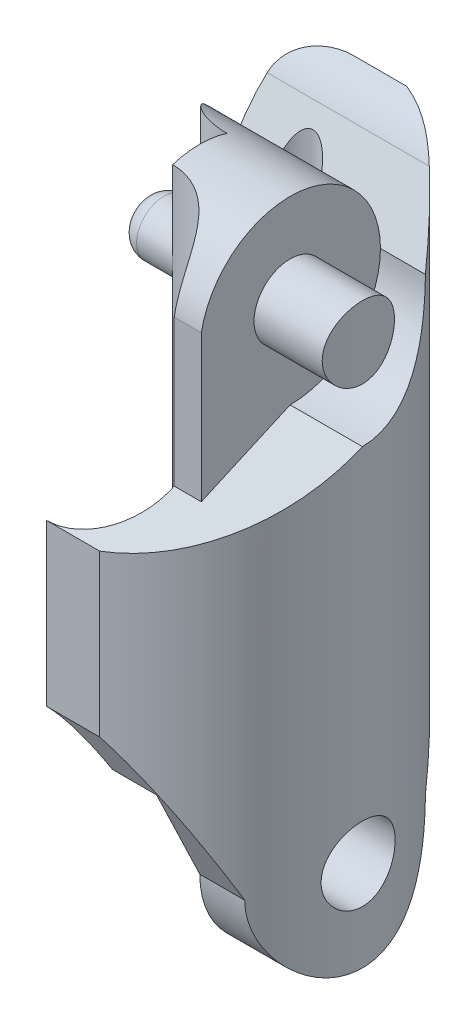
SolidWorks part; units mm, degrees
ref_plane "Front Plane" through (0, 0, 0) normal (0, 0, 1) x (1, 0, 0)
ref_plane "Top Plane" through (0, 0, 0) normal (0, 1, 0) x (1, 0, 0)
ref_plane "Right Plane" through (0, 0, 0) normal (1, 0, 0) x (0, 0, -1)
sketch "Sketch1" plane through (0, 0, 0) normal (0, 1, 0) x (1, 0, 0)
  line L0 (-2.958, 8.5) -> (2.958, 8.5)
  line L1 (-2.958, -8.5) -> (2.958, -8.5)
  arc A0 (-2.958, 8.5) -> (-2.958, -8.5) centre (0, 0) ccw
  arc A1 (2.958, 8.5) -> (2.958, -8.5) centre (0, 0) cw
  point P9 (-9, 0)
  point P10 (9, 0)
  dimension "D1" = 18
  dimension "D2" = 17
extrude "Boss-Extrude1" add sketch "Sketch1" along normal blind 35
sketch "Sketch2" plane through (0, 0, 0) normal (0, -1, 0) x (1, 0, 0)
  circle A0 centre (0, -5) radius 1.27
  circle A1 centre (0, 5) radius 1.27
  dimension "D1" = 2.54
  dimension "D2" = 5
  dimension "D3" = 5
extrude "Cut-Extrude1" cut sketch "Sketch2" against normal blind 35
sketch "Sketch3" plane through (0, 0, -8.5) normal (0, 0, -1) x (-1, 0, 0)
  line L0 (5, 0) -> (5, 10)
  line L1 (5, 10) -> (-5, 10)
  line L2 (-5, 10) -> (-5, 0)
  line L3 (5, 0) -> (-5, 0)
  line L4 (-2.958, 0) -> (2.958, 0) construction
  point P10 (0, 0)
  dimension "D1" = 10
  dimension "D2" = 10
extrude "Cut-Extrude2" cut sketch "Sketch3" against normal up to surface (17 mm away) up to face at (0, 17.5, 8.5)
sketch "Sketch4" plane through (5, 0, 0) normal (-1, 0, 0) x (0, 0, 1)
  line L0 (-7.4833, 10) -> (-5, 5)
  line L1 (8.5, 12.3086) -> (5, 5)
  line L2 (7.4833, 0) -> (-7.4833, 0) construction
  line L3 (-7.4833, 10) -> (-9.8579, -1.8222)
  line L4 (-9.8579, -1.8222) -> (9.8579, -1.8222)
  line L6 (8.5, 35) -> (8.5, 10) construction
  line L7 (9.8579, -1.8222) -> (8.5, 12.3086)
  arc A0 (-5, 5) -> (5, 5) centre (0, 5) ccw
  circle A1 centre (0, 5) radius 2.05
  point P7 (0, 0)
  dimension "D1" = 4.1
  dimension "D2" = 5
  dimension "D3" = 12.0584
  dimension "D4" = 37.769
extrude "Cut-Extrude3" cut sketch "Sketch4" against normal mid plane 35
ref_plane "Plane1" through (-2.958, 0, 0) normal (-1, 0, 0) x (0, 0, 1)
sketch "Sketch6" plane through (-2.958, 0, 0) normal (-1, 0, 0) x (0, 0, 1)
  line L0 (8.5, 21.2199) -> (0, 25)
  line L1 (8.5, 35) -> (8.5, 12.3086) construction
  line L2 (-5, 30) -> (-6.7559, 33.5353)
  line L3 (8.5, 35) -> (-8.5, 35) construction
  line L4 (8.5, 21.2199) -> (17.803, 42.886)
  line L6 (-7.4833, 10) -> (-5, 5) construction
  line L7 (-8.5, 35) -> (17.803, 42.886)
  arc A0 (0, 25) -> (-5, 30) centre (0, 30) cw
  circle A1 centre (0, 30) radius 2
  arc A2 (-6.7559, 33.5353) -> (-8.5, 35) centre (-9.3069, 32.2683) ccw
  dimension "D1" = 5
  dimension "D3" = 4
  dimension "D2" = 5
  dimension "D4" = 8.5
extrude "Cut-Extrude5" cut sketch "Sketch6" against normal blind 9.6 from surface starting at face at (5, 7.05, 0)
sketch "Sketch7" plane through (5, 0, 0) normal (1, 0, 0) x (0, 0, -1)
  line L0 (5, 30) -> (6.7559, 33.5353)
  line L2 (-8.3419, 47.5367) -> (-13.1682, 33.5285)
  line L3 (-7.4833, 35) -> (7.4833, 35) construction
  line L4 (-4.9155, 30.9155) -> (-4.9155, 22.814)
  line L5 (-7.4833, 21.6721) -> (0, 25) construction
  line L6 (-4.9155, 22.814) -> (-10.0468, 20.532)
  line L7 (-10.0468, 20.532) -> (-13.1682, 33.5285)
  line L8 (6.7559, 33.5353) -> (5, 30) construction
  line L9 (8.5, 35) -> (-8.3419, 47.5367)
  arc A0 (5, 30) -> (-4.9155, 30.9155) centre (0, 30) ccw
  arc A1 (6.7559, 33.5353) -> (8.5, 35) centre (9.3069, 32.2683) cw
  arc A2 (7.4833, 34.4564) -> (6.7559, 33.5353) centre (9.3069, 32.2683) ccw construction
  dimension "D1" = 5
fillet "Fillet3" radius 1 2 edges at (0, 10, -3.73) (0, 10, 6.27)
extrude "Cut-Extrude6" cut sketch "Sketch6<3>" along normal blind 6.604 from surface starting at face at (-5, 2.95, 0)
sketch "Sketch6<3>" plane through (-2.958, 0, 0) normal (-1, 0, 0) x (0, 0, 1) same geometry as "Sketch6"
extrude "Cut-Extrude7" cut sketch "Sketch7" against normal blind 14.986
sketch "Sketch8" plane through (0, 10, 0) normal (0, -1, 0) x (1, 0, 0)
  line L0 (0, 1.5) -> (0, -1.5)
  line L1 (-2.958, -8.5) -> (2.958, -8.5) construction
  line L2 (2.958, 8.5) -> (-2.958, 8.5) construction
  line L3 (0, 8.5) -> (-4.7901, 15.219)
  line L4 (-4.7901, 15.219) -> (-17.8556, -9.7177)
  line L5 (-17.8556, -9.7177) -> (-4.7901, -16.0136)
  line L6 (-4.7901, -16.0136) -> (0, -8.5)
  arc A0 (0, -1.5) -> (0, -8.5) centre (0, -5) ccw
  arc A1 (0, 1.5) -> (0, 8.5) centre (0, 5) ccw
  circle A2 centre (0, 5) radius 2.27 construction
  circle A3 centre (0, -5) radius 2.27 construction
  point P9 (0, 0)
  point P18 (0, 0)
extrude "Cut-Extrude8" cut sketch "Sketch8" against normal mid plane 62.992
sketch "Sketch9" plane through (0, 0, 0) normal (-1, 0, 0) x (0, 0, 1)
  line L0 (7.3945, 10) -> (-7.4833, 10) construction
  circle A0 centre (0, 16) radius 1.5
  dimension "D2" = 3
  dimension "D1" = 6
extrude "Cut-Extrude9" cut sketch "Sketch9" against normal blind 8.382
sketch "Sketch11" plane through (0, 0, 0) normal (-1, 0, 0) x (0, 0, 1)
  circle A0 centre (0, 16) radius 2
  dimension "D1" = 4
extrude "Cut-Extrude10" cut sketch "Sketch11" against normal mid plane 6.2
sketch "Sketch12" plane through (0, 0, 0) normal (-1, 0, 0) x (0, 0, 1)
  line L0 (0, 18) -> (0, 19.5)
  line L1 (0, 14) -> (0, 12.5)
  arc A0 (1.5, 17.3229) -> (-1.5, 17.3229) centre (0, 16) ccw construction
  arc A1 (-1.5, 14.6771) -> (1.5, 14.6771) centre (0, 16) ccw construction
  arc A2 (0, 19.5) -> (0, 12.5) centre (0, 16) cw
  arc A3 (1.5, 14.6771) -> (1.5, 17.3229) centre (0, 16) ccw construction
  arc A4 (0, 18) -> (0, 14) centre (0, 16) cw
  point P17 (0, 14)
  dimension "D1" = 1.5
extrude "Boss-Extrude2" add sketch "Sketch12" against normal blind 3.862
sketch "Sketch13" plane through (0, 0, 0) normal (-1, 0, 0) x (0, 0, 1)
  line L0 (1.5, 34.7697) -> (1.5, 19.1623) construction
  circle A0 centre (0, 30) radius 1.5
  circle A1 centre (0, 30) radius 2 construction
extrude "Boss-Extrude4" add sketch "Sketch13" along normal blind 3
fillet "Fillet5" radius 1 1 edges at (-3, 30, 1.5)
